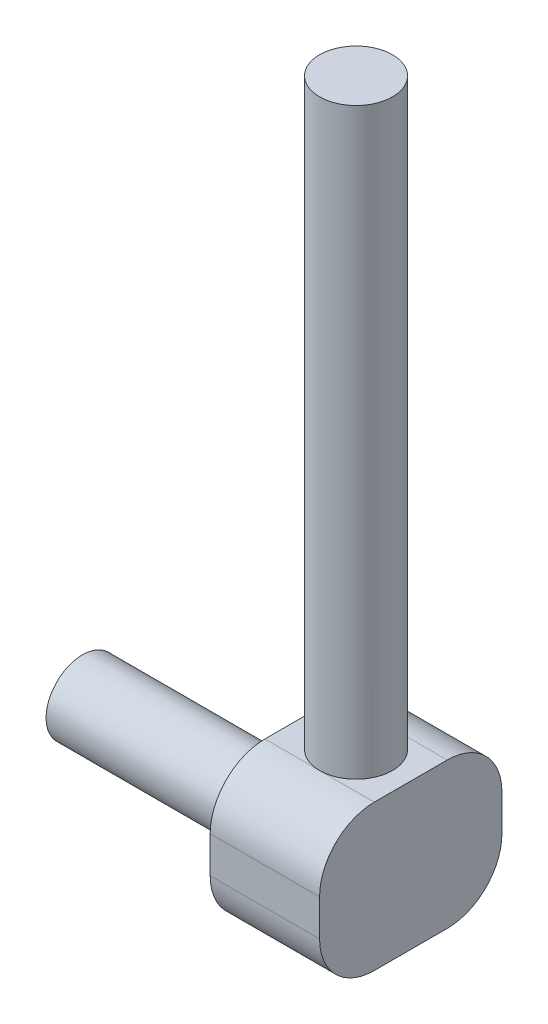
SolidWorks part; units mm, degrees
ref_plane "前视基准面" through (0, 0, 0) normal (0, 0, 1) x (1, 0, 0)
ref_plane "上视基准面" through (0, 0, 0) normal (0, 1, 0) x (1, 0, 0)
ref_plane "右视基准面" through (0, 0, 0) normal (1, 0, 0) x (0, 0, -1)
sketch "草图1" plane through (0, 0, 0) normal (0, 1, 0) x (1, 0, 0)
  circle A0 centre (0, 0) radius 10
  dimension "D1" = 20
extrude "凸台-拉伸1" add sketch "草图1" along normal blind 200
sketch "草图2" plane through (0, 0, 0) normal (1, 0, 0) x (0, 0, -1)
  line L1 (-10, 40) -> (10, 40)
  line L2 (-25, 25) -> (-25, 15)
  line L3 (-10, 0) -> (10, 0)
  line L4 (25, 25) -> (25, 15)
  arc A0 (10, 0) -> (25, 15) centre (10, 15) ccw
  arc A1 (-10, 0) -> (-25, 15) centre (-10, 15) cw
  arc A2 (25, 25) -> (10, 40) centre (10, 25) ccw
  arc A3 (-10, 40) -> (-25, 25) centre (-10, 25) ccw
  dimension "D4" = 15
  dimension "D1" = 50
  dimension "D2" = 25
  dimension "D3" = 40
extrude "凸台-拉伸2" add sketch "草图2" along normal blind 15 and the other way blind 15
sketch "草图4" plane through (-15, 0, 0) normal (-1, 0, 0) x (0, 0, 1)
  circle A0 centre (0, 15) radius 10
  point P2 (0, 16.1194)
  dimension "D1" = 20
  dimension "D2" = 15
extrude "凸台-拉伸3" add sketch "草图4" along normal blind 60
